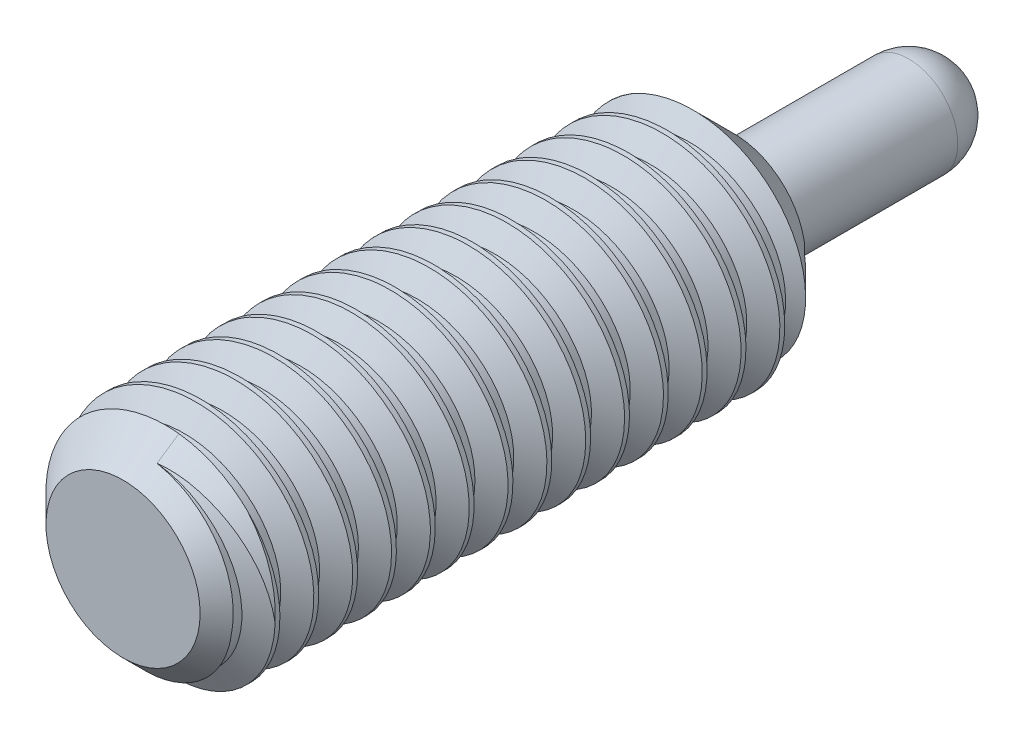
SolidWorks part; units mm, degrees
material "AISI 304"
ref_plane "Front Plane" through (0, 0, 0) normal (0, 0, 1) x (1, 0, 0)
ref_plane "Top Plane" through (0, 0, 0) normal (0, 1, 0) x (1, 0, 0)
ref_plane "Right Plane" through (0, 0, 0) normal (1, 0, 0) x (0, 0, -1)
sketch "Sketch1" plane through (0, 0, 0) normal (0, 0, 1) x (1, 0, 0)
  circle A0 centre (0, 0) radius 2.0828
  dimension "D1" = 4.1656
extrude "Boss-Extrude1" add sketch "Sketch1" along normal blind 11.0998
thread "Thread1" pitch 0.7056 method cut profile "Thread Profile1" start angle 0, offset 1, length 0, pitch 0.7056, diameter 4.1656
ref_plane "Plane1" through (-2.0828, 0, 12.0998) normal (0, -1, 0) x (-1, 0, 0)
sketch "Thread Profile1" plane through (-2.0828, 0, 12.0998) normal (0, -1, 0) x (-1, 0, 0)
  line L0 (0, 0) -> (0, 0.7056) construction
  line L11 (0, 0) -> (0, 0.6174)
  line L12 (0, 0.6174) -> (-0.3819, 0.3969)
  line L13 (-0.3819, 0.3969) -> (-0.3819, 0.2205)
  line L15 (-0.3819, 0.2205) -> (0, 0)
  line L17 (-0.3819, 0.3087) -> (0, 0.3087) construction
  point P2 (0, 0)
  dimension "Pitch" = 0.7056
  dimension "Profile_Angle" = 60
  dimension "Profile_Land" = 0.1764
  dimension "Profile_Height" = 0.3819
sketch "Sketch5" plane through (0, 0, 0) normal (0, 1, 0) x (1, 0, 0)
  line L0 (0, 0) -> (0, 4.064)
  line L1 (0, 4.064) -> (0.889, 4.064)
  line L2 (0.889, 4.064) -> (0.889, 0)
  line L3 (0.889, 0) -> (0, 0)
  circle A0 centre (0, 3.175) radius 0.889
  dimension "D1" = 0.889
  dimension "D2" = 4.064
revolve "Revolve1" add sketch "Sketch5" angle 360 about L0 region at (0.4634, 0, -1.2463) region at (0.3773, 0, -3.175)
sketch "Sketch6" plane through (0, 0, 0) normal (1, 0, 0) x (0, 0, -1)
  line L0 (0, 1.3) -> (-2, 3.3)
  line L1 (-2, 3.3) -> (0, 3.3)
  line L2 (0, 3.3) -> (0, 1.3)
  line L3 (0, 0) -> (4.064, 0) construction
  line L4 (0, 0) -> (-12.5, 0) construction
  line L6 (0, 1.3) -> (0, 3.3)
  line L9 (-12.5, 0) -> (-9.5, 3)
  line L10 (-9.5, 3) -> (-12.5, 3)
  line L11 (-12.5, 3) -> (-12.5, 0)
  line L12 (-12.5, 0) -> (-12, 0)
  line L13 (-12, 0) -> (-12, 0.5)
  arc A0 (3.175, -0.889) -> (3.175, 0.889) centre (3.175, 0) ccw construction
  dimension "D1" = 45
  dimension "D2" = 1.3
  dimension "D3" = 2
  dimension "D6" = 45
  dimension "D7" = 3
  dimension "D8" = 12.5
  dimension "D9" = 0.5
revolve "Cut-Revolve3" cut sketch "Sketch6" angle 360 about L3 region at (0, 2.6333, 0.6667) region at (0, 2, 11.5) region at (0, 0.1667, 12.1667)
sketch "Sketch8" plane through (0, 0, 0) normal (0, 0, -1) x (-1, 0, 0)
  line L1 (-2.0677, -0.25) -> (2.0677, -0.25)
  line L2 (-2.0677, -0.25) -> (-2.0677, 0.25)
  line L3 (-2.0677, 0.25) -> (2.0677, 0.25)
  line L4 (2.0677, -0.25) -> (2.0677, 0.25)
  line L5 (-2.0677, -0.25) -> (2.0677, 0.25) construction
  line L6 (-2.0677, 0.25) -> (2.0677, -0.25) construction
  circle A0 centre (0, 0) radius 2.0828 construction
  circle A1 centre (0, 0) radius 0.889
  circle A2 centre (0, 0) radius 0.889 construction
  point P0 (0, 0)
  circle M6 centre (0, 0) radius 0.889
  circle M12 centre (0, 0) radius 1.3
  dimension "D1" = 0.5
extrude "Cut-Extrude1" cut sketch "Sketch8" against normal blind 0.2 contours L3 L1 M6 | L3 L1 M6 | L3 L2 L1 M12 | L1 L4 L3 M12 region at (1.6798, 0, 0) region at (1.0845, 0, 0) region at (-1.6798, 0, 0) region at (-1.0845, 0, 0)
